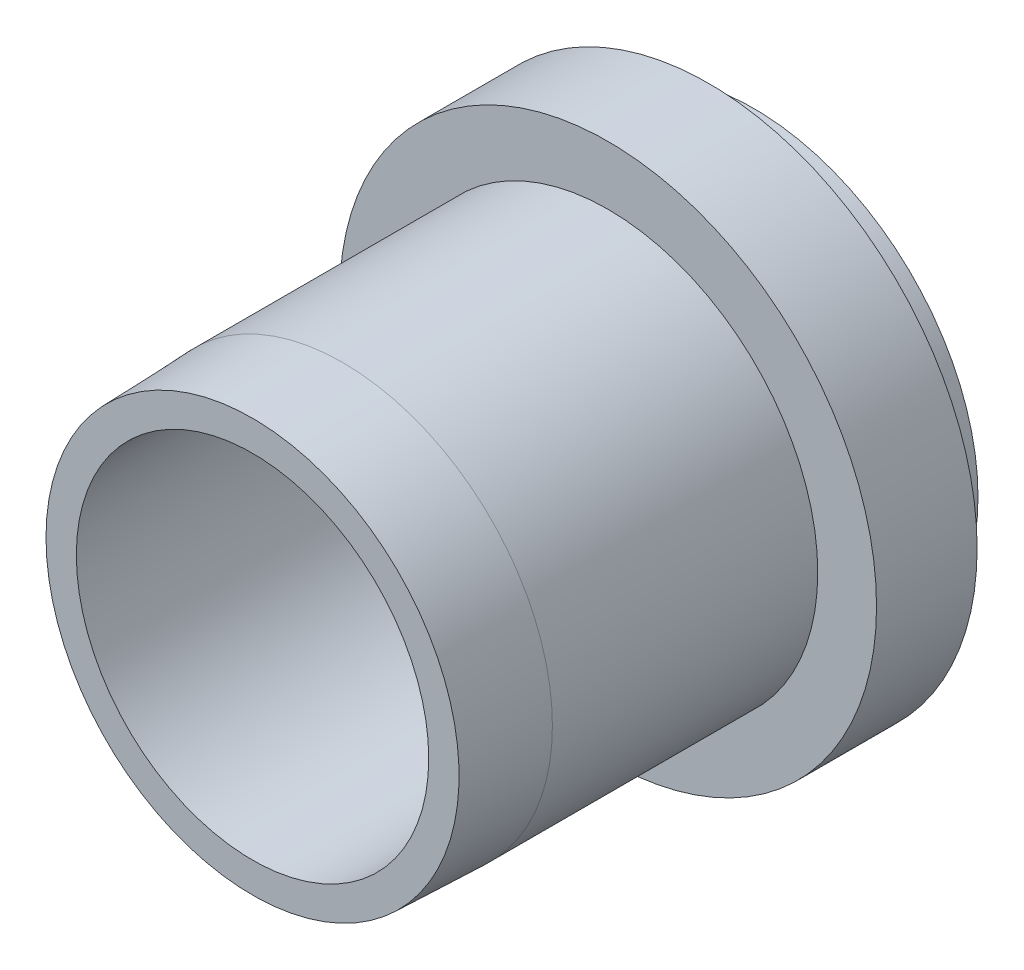
SolidWorks part; units mm, degrees
material "PF"
ref_plane "Front Plane" through (0, 0, 0) normal (0, 0, 1) x (1, 0, 0)
ref_plane "Top Plane" through (0, 0, 0) normal (0, 1, 0) x (1, 0, 0)
ref_plane "Right Plane" through (0, 0, 0) normal (1, 0, 0) x (0, 0, -1)
sketch "Sketch2" plane through (0, 0, 0) normal (0, 0, 1) x (1, 0, 0)
  circle A0 centre (0, 0) radius 6.465
  dimension "D1" = 12.93
extrude "Boss-Extrude1" add sketch "Sketch2" along normal blind 4.2
sketch "Sketch3" plane through (0, 0, 4.2) normal (0, 0, 1) x (1, 0, 0)
  circle A0 centre (0, 0) radius 7.74
  dimension "D1" = 15.48
extrude "Boss-Extrude2" add sketch "Sketch3" against normal blind 2.9
sketch "Sketch4" plane through (0, 0, 4.2) normal (0, 0, 1) x (1, 0, 0)
  circle A0 centre (0, 0) radius 6.0452
  dimension "D1" = 12.0904
extrude "Boss-Extrude3" add sketch "Sketch4" along normal offset from surface (10.25 mm away) 14.45 contours A0 up to face at (6.465, 0, 0)
sketch "Sketch5" plane through (0, 0, 14.45) normal (0, 0, 1) x (1, 0, 0)
  circle A0 centre (0, 0) radius 5.08
  dimension "D1" = 10.16
extrude "Cut-Extrude1" cut sketch "Sketch5" against normal through all
sketch "Sketch6" plane through (0, 0, 0) normal (1, 0, 0) x (0, 0, -1)
  line L0 (-14.45, 5.9544) -> (-11.85, 6.0452)
  line L2 (-4.2, 6.0452) -> (-14.45, 6.0452) construction
  line L3 (-11.85, 6.0452) -> (-14.45, 6.0452)
  line L4 (-14.45, 6.0452) -> (-14.45, 5.9544)
  line L5 (-14.45, 5.9544) -> (-14.45, 5.08)
  line L6 (0, 0) -> (-19.8152, 0) construction
  dimension "D1" = 2.6
  dimension "D2" = 2
revolve "Cut-Revolve1" cut sketch "Sketch6" angle 360 about L6
